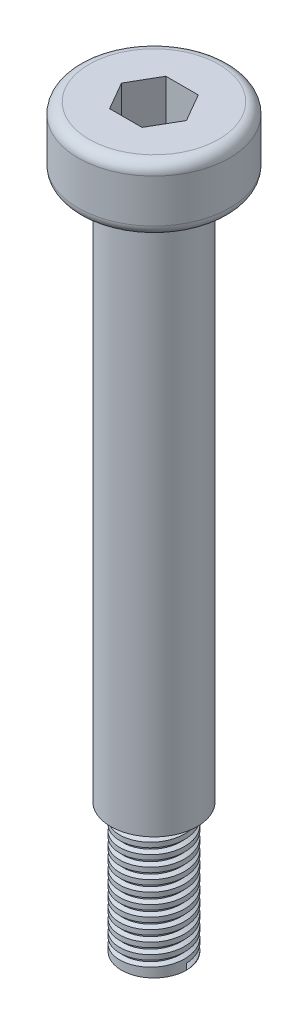
SolidWorks part; units mm, degrees
ref_plane "Front Plane" through (0, 0, 0) normal (0, 0, 1) x (1, 0, 0)
ref_plane "Top Plane" through (0, 0, 0) normal (0, 1, 0) x (1, 0, 0)
ref_plane "Right Plane" through (0, 0, 0) normal (1, 0, 0) x (0, 0, -1)
sketch "Sketch8" plane through (0, 0, 0) normal (0, 1, 0) x (1, 0, 0)
  circle A0 centre (0, 0) radius 1.5
extrude "Boss-Extrude4" add sketch "Sketch8" along normal blind 6 separate body
sketch "Sketch9" plane through (0, 6, 0) normal (0, 1, 0) x (1, 0, 0)
  circle A0 centre (0, 0) radius 2
extrude "Boss-Extrude5" add sketch "Sketch9" along normal blind 25
sketch "Sketch10" plane through (0, 31, 0) normal (0, 1, 0) x (1, 0, 0)
  circle A0 centre (0, 0) radius 3.5
extrude "Boss-Extrude6" add sketch "Sketch10" along normal blind 3
sketch "Sketch11" plane through (0, 34, 0) normal (0, 1, 0) x (1, 0, 0)
  line L1 (1.5, 0) -> (0.75, 1.299)
  line L2 (0.75, 1.299) -> (-0.75, 1.299)
  line L3 (-0.75, 1.299) -> (-1.5, 0)
  line L4 (-1.5, 0) -> (-0.75, -1.299)
  line L5 (-0.75, -1.299) -> (0.75, -1.299)
  line L6 (0.75, -1.299) -> (1.5, 0)
  circle A0 centre (0, 0) radius 1.299 construction
  point P1 (0, 0)
extrude "Cut-Extrude3" cut sketch "Sketch11" against normal blind 2
fillet "Fillet2" radius 0.5 2 edges at (0, 34, 3.5) (0, 31, 3.5)
thread "Thread2" pitch 0.3175 method cut profile "Thread Profile2" start angle 0, offset 0, length 6, pitch 0.5, diameter 3
ref_plane "Plane2" through (1.5, 0, 0) normal (0, 0, 1) x (1, 0, 0)
sketch "Thread Profile2" plane through (1.5, 0, 0) normal (0, 0, 1) x (1, 0, 0)
  line L0 (0, 0) -> (0, 0.3175) construction
  line L11 (0, 0) -> (0, 0.2778)
  line L12 (0, 0.2778) -> (-0.1719, 0.1786)
  line L13 (-0.1719, 0.1786) -> (-0.1719, 0.0992)
  line L15 (-0.1719, 0.0992) -> (0, 0)
  line L17 (-0.1719, 0.1389) -> (0, 0.1389) construction
  point P2 (0, 0)
  dimension "Pitch" = 0.3175
  dimension "Profile_Angle" = 60
  dimension "Profile_Land" = 0.0794
  dimension "Profile_Height" = 0.1719
